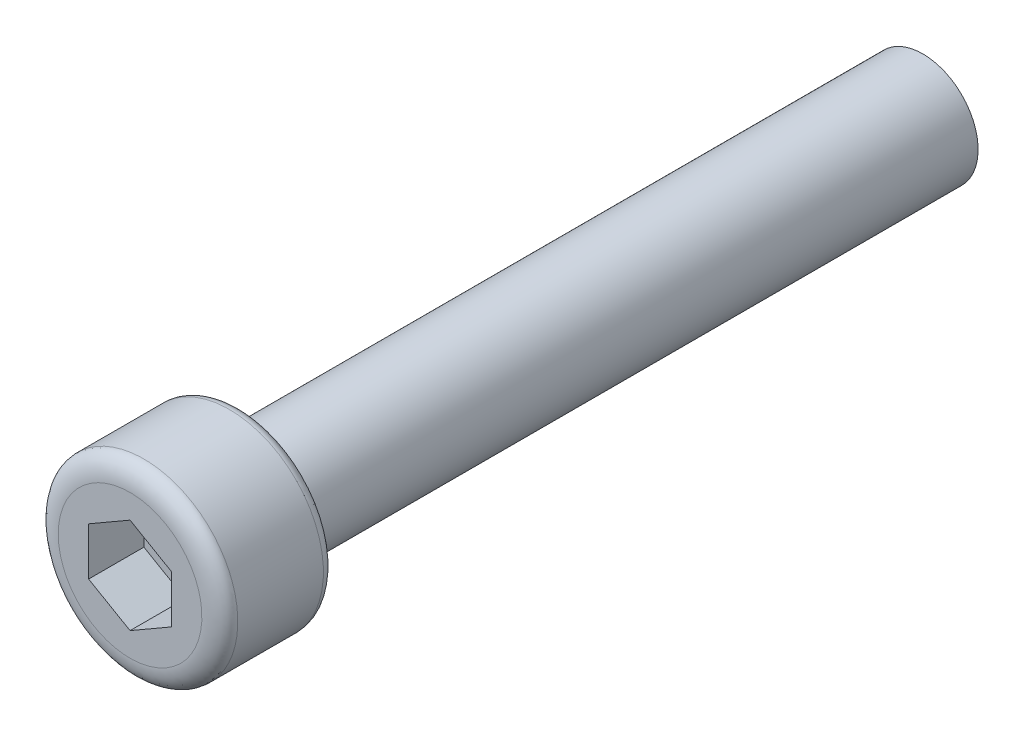
SolidWorks part; units mm, degrees
ref_plane "前视基准面" through (0, 0, 0) normal (0, 0, 1) x (1, 0, 0)
ref_plane "上视基准面" through (0, 0, 0) normal (0, 1, 0) x (1, 0, 0)
ref_plane "右视基准面" through (0, 0, 0) normal (1, 0, 0) x (0, 0, -1)
sketch "草图2" plane through (0, 0, 0) normal (1, 0, 0) x (0, 0, -1)
  line L0 (-14.5, 0) -> (-14.5, 3.4)
  line L1 (-14.5, 3.4) -> (-10.5, 3.4)
  line L2 (-10.5, 3.4) -> (-10.5, 2)
  line L3 (-10.5, 2) -> (14.5, 2)
  line L4 (14.5, 2) -> (14.5, 0)
  line L5 (14.5, 0) -> (-14.5, 0)
  dimension "D1" = 25
  dimension "D2" = 3.4
  dimension "D3" = 2
  dimension "D4" = 4
revolve "旋转1" add sketch "草图2" angle 360 about L5
chamfer "倒角1" distance 0.3 angle 60 1 edges at (-2, 0, -14.5) first distance on face at (-2, 0, 10.5)
fillet "圆角1" radius 0.4 1 edges at (-3.4, 0, 10.5)
fillet "圆角2" radius 0.8 1 edges at (-3.4, 0, 14.5) second distance 0.5 first distance on face at (-3.4, 0, 14.5)
sketch "草图3" plane through (0, 0, 14.5) normal (0, 0, 1) x (1, 0, 0)
  line L1 (0, 1.7321) -> (-1.5, 0.866)
  line L2 (-1.5, 0.866) -> (-1.5, -0.866)
  line L3 (-1.5, -0.866) -> (0, -1.7321)
  line L4 (0, -1.7321) -> (1.5, -0.866)
  line L5 (1.5, -0.866) -> (1.5, 0.866)
  line L6 (1.5, 0.866) -> (0, 1.7321)
  circle A0 centre (0, 0) radius 1.5 construction
  dimension "D1" = 3
extrude "切除-拉伸1" cut sketch "草图3" against normal blind 2
